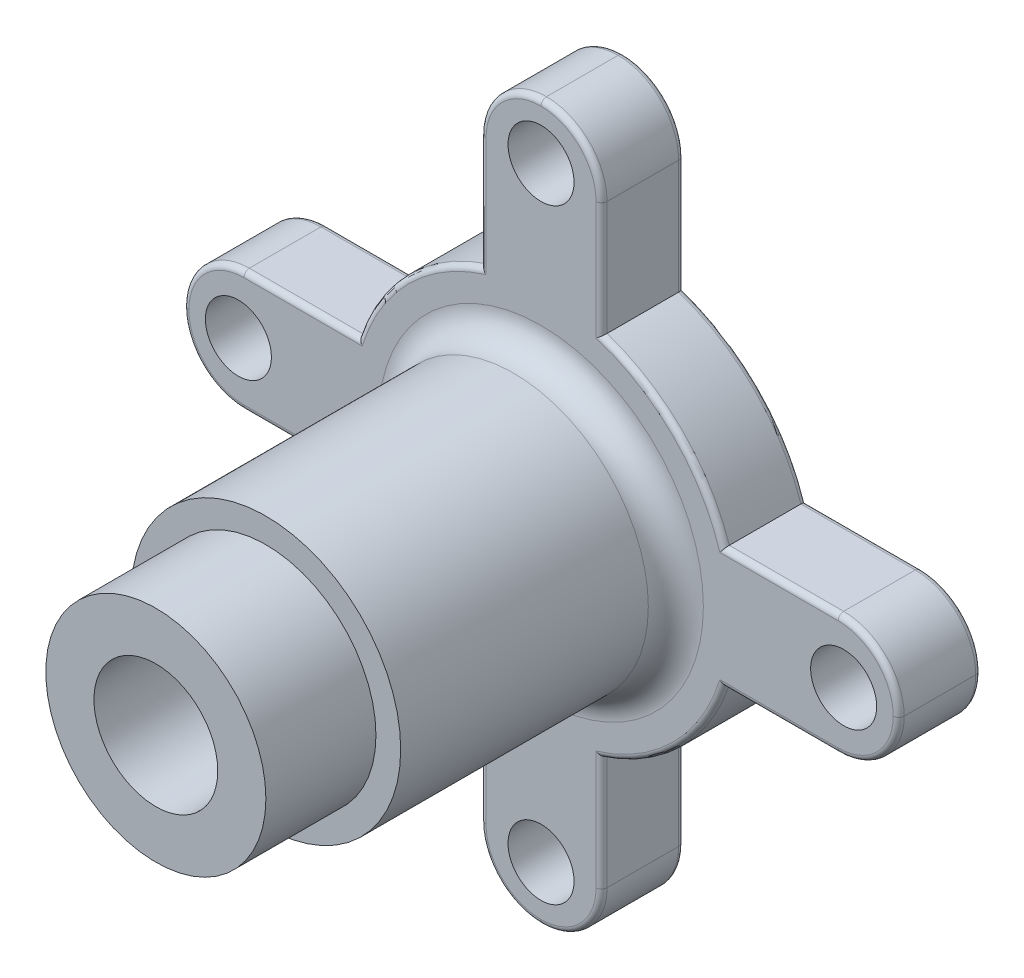
SolidWorks part; units mm, degrees
material "6061-O (SS)"
ref_plane "Front Plane" through (0, 0, 0) normal (0, 0, 1) x (1, 0, 0)
ref_plane "Top Plane" through (0, 0, 0) normal (0, 1, 0) x (1, 0, 0)
ref_plane "Right Plane" through (0, 0, 0) normal (1, 0, 0) x (0, 0, -1)
sketch "Sketch1" plane through (0, 0, 0) normal (0, 0, 1) x (1, 0, 0)
  line L5 (-11, -33.2265) -> (-11, -65)
  line L6 (-65, -11) -> (-33.2265, -11)
  line L11 (-65, -11) -> (-65, 11)
  line L12 (-65, 11) -> (-33.2265, 11)
  line L24 (65, -11) -> (65, 11)
  line L25 (11, -33.2265) -> (11, -65)
  line L28 (33.2265, -11) -> (65, -11)
  line L29 (-11, 65) -> (11, 65)
  line L30 (-11, 65) -> (-11, 33.2265)
  line L31 (-11, -65) -> (11, -65)
  line L32 (11, 65) -> (11, 33.2265)
  line L33 (33.2265, 11) -> (65, 11)
  circle A2 centre (0, 0) radius 55 construction
  circle A3 centre (0, 55) radius 6
  circle A4 centre (55, 0) radius 6
  circle A5 centre (0, -55) radius 6
  circle A6 centre (-55, 0) radius 6
  arc A7 (-11, 33.2265) -> (-33.2265, 11) centre (0, 0) ccw
  arc A9 (11, -33.2265) -> (33.2265, -11) centre (0, 0) ccw
  arc A10 (33.2265, 11) -> (11, 33.2265) centre (0, 0) ccw
  arc A11 (-33.2265, -11) -> (-11, -33.2265) centre (0, 0) ccw
  circle A12 centre (0, 0) radius 20
  dimension "D1" = 110
  dimension "D2" = 22
  dimension "D3" = 65
  dimension "D4" = 65
  dimension "D5" = 65
  dimension "65mm" = 65
extrude "Boss-Extrude1" add sketch "Sketch1" along normal blind 15 contours A3 A4 A5 A6 region at (-23.4487, -23.4487, 0)
sketch "Sketch5" plane through (0, 0, 15) normal (0, 0, 1) x (1, 0, 0)
  circle A0 centre (0, 0) radius 20
  circle A1 centre (0, 0) radius 24.5
  dimension "D1" = 49
extrude "Boss-Extrude2" add sketch "Sketch5" along normal blind 50
sketch "Sketch7" plane through (0, 0, 65) normal (0, 0, 1) x (1, 0, 0)
  circle A0 centre (0, 0) radius 20
  circle A1 centre (0, 0) radius 11.25
extrude "Boss-Extrude3" add sketch "Sketch7" along normal blind 20 separate body
fillet "Fillet1" radius 11 8 edges at (-65, 11, 7.5) (-65, -11, 7.5) (-11, -65, 7.5) (11, -65, 7.5) (-11, 65, 7.5) (11, 65, 7.5) (65, -11, 7.5) (65, 11, 7.5)
fillet "Fillet2" radius 5 1 edges at (24.5, 0, 15)
fillet "Fillet3" radius 1 20 edges at (-61.7782, -7.7782, 15) (-61.7782, 7.7782, 15) (-7.7782, -61.7782, 15) (7.7782, -61.7782, 15) (61.7782, -7.7782, 15) (61.7782, 7.7782, 15) (7.7782, 61.7782, 15) (-7.7782, 61.7782, 15) (-43.6132, -11, 15) (-24.7487, 24.7487, 15) (-43.6132, 11, 15) (-24.7487, -24.7487, 15) (-11, -43.6132, 15) (24.7487, -24.7487, 15) (11, -43.6132, 15) (43.6132, -11, 15) (43.6132, 11, 15) (24.7487, 24.7487, 15) (11, 43.6132, 15) (-11, 43.6132, 15)
fillet "Fillet4" radius 1 20 edges at (-61.7782, 7.7782, 0) (-61.7782, -7.7782, 0) (-7.7782, -61.7782, 0) (7.7782, -61.7782, 0) (61.7782, -7.7782, 0) (61.7782, 7.7782, 0) (7.7782, 61.7782, 0) (-7.7782, 61.7782, 0) (-24.7487, 24.7487, 0) (-43.6132, 11, 0) (-43.6132, -11, 0) (-24.7487, -24.7487, 0) (-11, -43.6132, 0) (11, -43.6132, 0) (24.7487, -24.7487, 0) (43.6132, -11, 0) (43.6132, 11, 0) (24.7487, 24.7487, 0) (11, 43.6132, 0) (-11, 43.6132, 0)
